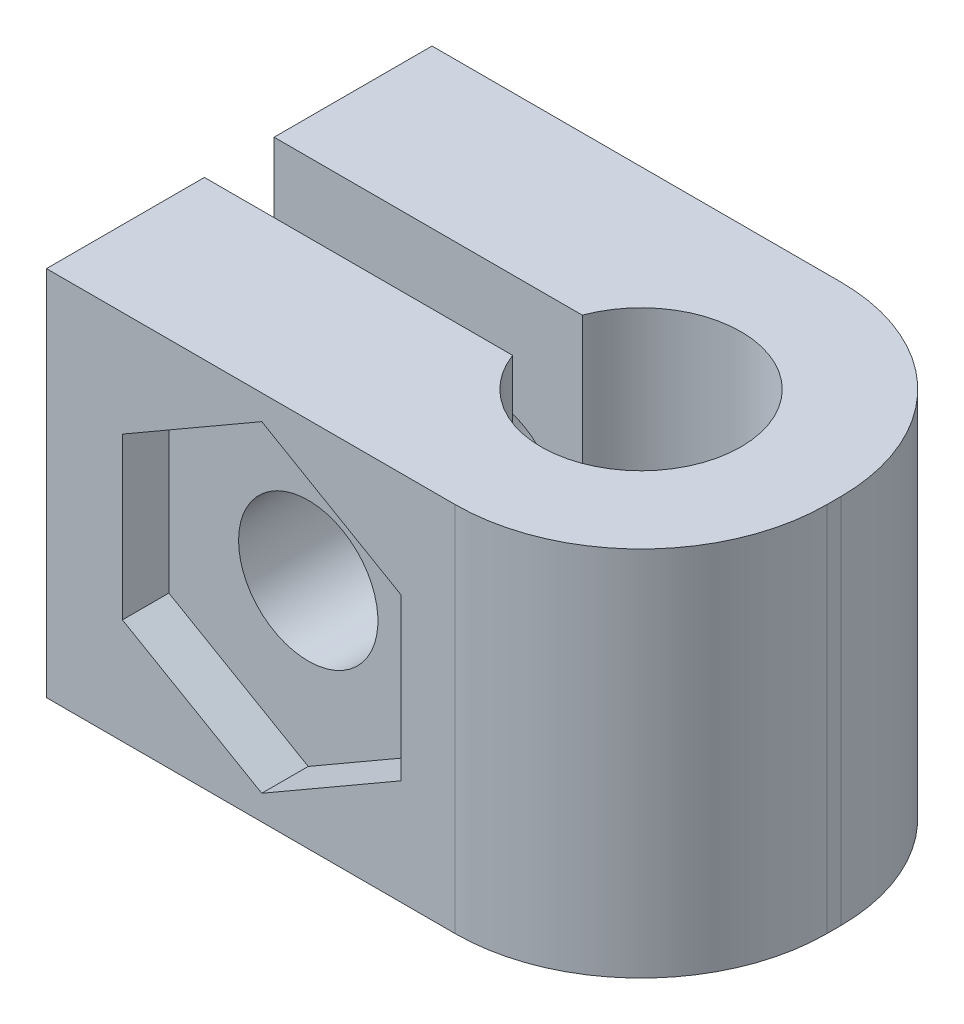
SolidWorks part; units mm, degrees
ref_plane "Front Plane" through (0, 0, 0) normal (0, 0, 1) x (1, 0, 0)
ref_plane "Top Plane" through (0, 0, 0) normal (0, 1, 0) x (1, 0, 0)
ref_plane "Right Plane" through (0, 0, 0) normal (1, 0, 0) x (0, 0, -1)
sketch "Sketch1" plane through (0, 0, 0) normal (0, 1, 0) x (1, 0, 0)
  line L0 (-2.15, 0) -> (-8.65, 0) construction
  line L1 (-4.15, 0) -> (-4.15, -4.15) construction
  line L2 (-8.65, -4.15) -> (4.15, -4.15)
  line L3 (-8.65, -4.15) -> (-8.65, 4.15)
  line L4 (-8.65, 4.15) -> (4.15, 4.15)
  line L5 (4.15, -4.15) -> (4.15, 4.15)
  line L7 (-8.65, -0.75) -> (-2.0149, -0.75)
  line L8 (-8.65, -0.75) -> (-8.65, 0.75)
  line L9 (-8.65, 0.75) -> (-2.0149, 0.75)
  line L10 (-2.0149, -0.75) -> (-2.0149, 0.75)
  line L11 (-5.65, 0) -> (-2.65, 0) construction
  line L12 (-5.65, 0) -> (-5.65, -4.15) construction
  line L13 (-5.65, -4.15) -> (-2.65, -4.15) construction
  line L14 (-2.65, 0) -> (-2.65, -4.15) construction
  line L15 (-5.65, 0) -> (-2.65, -4.15) construction
  line L16 (-5.65, -4.15) -> (-2.65, 0) construction
  circle A0 centre (0, 0) radius 2.15
  point P9 (-2.15, 0)
  point P16 (2.15, 0)
  point P17 (-4.15, -2.075)
  point P23 (0, -2.15)
  dimension "D2" = 4.3
  dimension "D1" = 1.5
  dimension "D3" = 3
  dimension "D4" = 3
  dimension "D5" = 0.5
  dimension "D6" = 2
  dimension "D7" = 2
extrude "Boss-Extrude1" add sketch "Sketch1" along normal blind 8 contours A0 L7 L3 L2 L5 L4 L9 region at (-8.4974, 0, 2.45)
sketch "Sketch2" plane through (0, 0, -0.75) normal (0, 0, 1) x (1, 0, 0)
  line L0 (-2.0149, 4) -> (-2.5149, 4) construction
  line L1 (-4.0149, 4) -> (-4.0149, 7.4641) construction
  line L2 (-4.0149, 7.4641) -> (-7.0149, 5.7321)
  line L3 (-7.0149, 5.7321) -> (-7.0149, 2.2679)
  line L4 (-8.65, 0) -> (-2.0149, 0)
  line L5 (-2.0149, 0) -> (-2.0149, 8)
  line L6 (-2.0149, 8) -> (-8.65, 8)
  line L7 (-8.65, 8) -> (-8.65, 0)
  line L8 (-8.65, 0) -> (-2.0149, 0)
  line L9 (-2.0149, 0) -> (-2.0149, 8)
  line L10 (-2.0149, 8) -> (-8.65, 8)
  line L11 (-8.65, 8) -> (-8.65, 0)
  line L12 (-7.0149, 2.2679) -> (-4.0149, 0.5359)
  line L13 (-4.0149, 0.5359) -> (-1.0149, 2.2679)
  line L14 (-1.0149, 2.2679) -> (-1.0149, 5.7321)
  line L15 (-1.0149, 5.7321) -> (-4.0149, 7.4641)
  circle A0 centre (-4.0149, 4) radius 1.5
  circle A1 centre (-4.0149, 4) radius 3 construction
  dimension "D2" = 3
  dimension "D3" = 0.5
  dimension "D4" = 6
  dimension "D1" = 0
extrude "Cut-Extrude1" cut sketch "Sketch2" against normal through all both and the other way through all contours A0 region at (-4.0149, 4, -0.75)
extrude "Cut-Extrude2" cut sketch "Sketch2<3>" against normal blind 1 from surface contours L9 L15 L2 L3 L12 L13 A0 | L14 L15 L9 L13 region at (-3.0577, 6.8128, -0.75) region at (-1.5388, 4, -0.75) starting at face at (-2.5149, 4, 4.15)
sketch "Sketch2<3>" plane through (0, 0, -0.75) normal (0, 0, 1) x (1, 0, 0) same geometry as "Sketch2"
sketch "Sketch3" plane through (0, 0, -4.15) normal (0, 0, -1) x (-1, 0, 0)
  circle A0 centre (4.0149, 4) radius 3
  dimension "D1" = 6
extrude "Cut-Extrude3" cut sketch "Sketch3" against normal blind 1
fillet "Fillet1" radius 4 2 edges at (4.15, 4, 4.15) (4.15, 4, -4.15)
